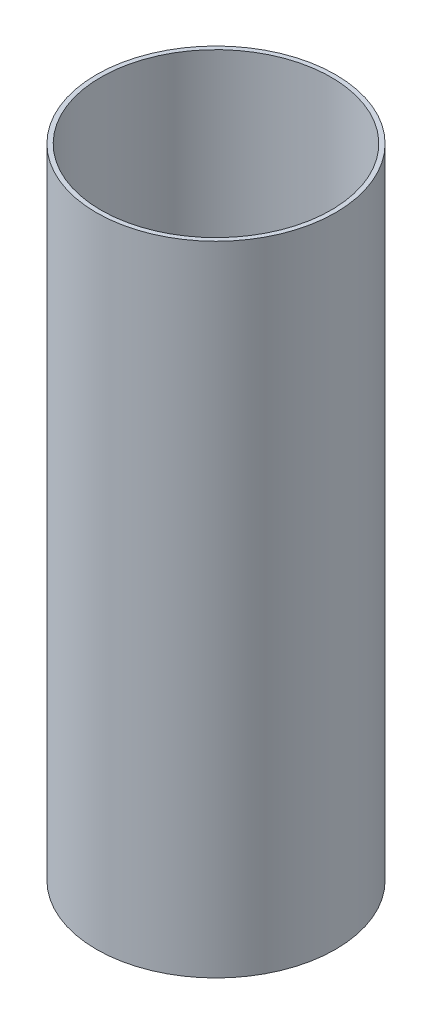
SolidWorks part; units mm, degrees
material "E-Glass Fiber"
ref_plane "Front Plane" through (0, 0, 0) normal (0, 0, 1) x (1, 0, 0)
ref_plane "Top Plane" through (0, 0, 0) normal (0, 1, 0) x (1, 0, 0)
ref_plane "Right Plane" through (0, 0, 0) normal (1, 0, 0) x (0, 0, -1)
sketch "Coupler Profile" plane through (0, 0, 0) normal (0, 1, 0) x (1, 0, 0)
  circle A0 centre (0, 0) radius 73.3425
  circle A1 centre (0, 0) radius 76.1746
  dimension "D1" = 146.685
  dimension "D2" = 152.3492
extrude "Coupler Body" add sketch "Coupler Profile" along normal blind 406.4
equation "\"Length\"=16"
equation "\"Outer Diameter\"= 5.998"
equation "\"Inner Diameter\"= 5.775"
equation "\"Wall Thickness\"= 0.111"
equation "\"D1@Coupler Profile\" = \"Inner Diameter\""
equation "\"D2@Coupler Profile\" = \"Outer Diameter\""
equation "\"D1@Coupler Body\" = \"Length\""
